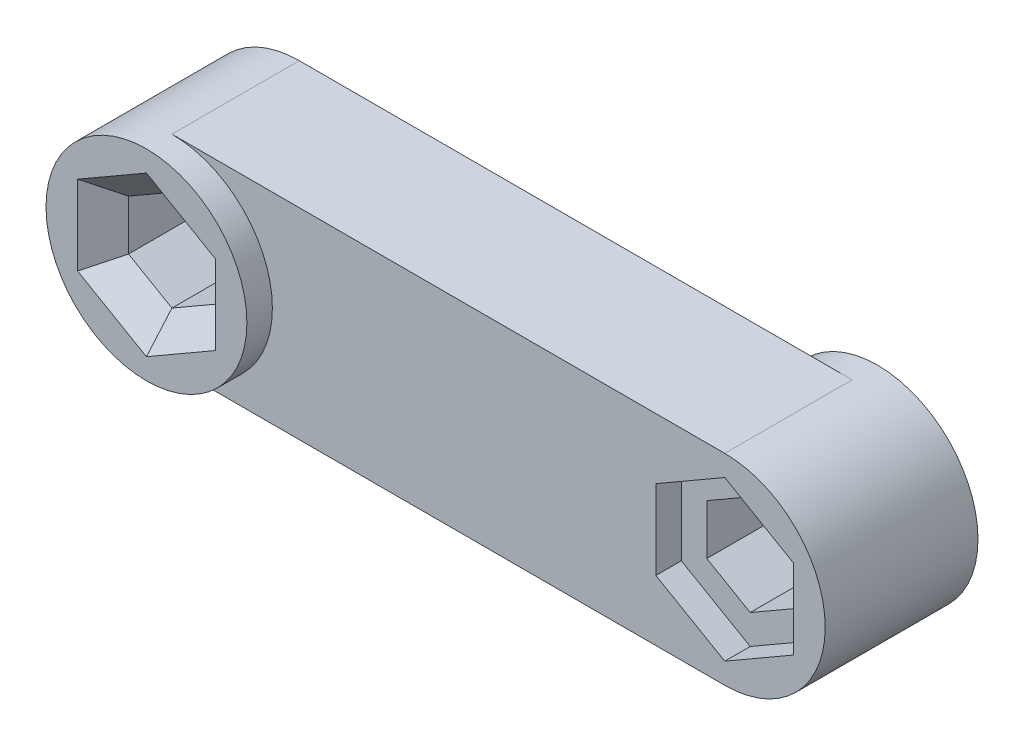
SolidWorks part; units mm, degrees
ref_plane "Plan de face" through (0, 0, 0) normal (1, 0, 0) x (0, 1, 0)
ref_plane "Plan de dessus" through (0, 0, 0) normal (0, 0, 1) x (0, 1, 0)
ref_plane "Plan de droite" through (0, 0, 0) normal (0, 1, 0) x (-1, 0, 0)
sketch "Esquisse1" plane through (0, 0, 0) normal (0, 0, 1) x (0, 1, 0)
  line L0 (0, -21.71) -> (0, 21.71) construction
  line L1 (-7.89, -21.71) -> (-7.89, 21.71)
  line L2 (7.89, -21.71) -> (7.89, 21.71)
  line L3 (0, 0) -> (50.7117, 0) construction
  line L4 (-1.9688, -18.3) -> (-3.9375, -21.71)
  line L5 (-3.9375, -21.71) -> (-1.9688, -25.12)
  line L6 (-1.9688, -25.12) -> (1.9688, -25.12)
  line L7 (1.9688, -25.12) -> (3.9375, -21.71)
  line L8 (3.9375, -21.71) -> (1.9688, -18.3)
  line L9 (1.9688, -18.3) -> (-1.9688, -18.3)
  line L10 (1.9688, 18.3) -> (-1.9688, 18.3)
  line L11 (3.9375, 21.71) -> (1.9688, 18.3)
  line L12 (1.9688, 25.12) -> (3.9375, 21.71)
  line L13 (-1.9688, 25.12) -> (1.9688, 25.12)
  line L14 (-3.9375, 21.71) -> (-1.9688, 25.12)
  line L15 (-1.9688, 18.3) -> (-3.9375, 21.71)
  arc A0 (-7.89, -21.71) -> (7.89, -21.71) centre (0, -21.71) ccw
  arc A1 (7.89, 21.71) -> (-7.89, 21.71) centre (0, 21.71) ccw
  circle A2 centre (0, -21.71) radius 3.41 construction
  circle A3 centre (0, 21.71) radius 3.41 construction
  point P2 (0, 0)
  dimension "D1" = 43.42
  dimension "D2" = 15.78
  dimension "D3" = 6.82
extrude "Boss.-Extru.1" add sketch "Esquisse1" along normal blind 10
sketch "Esquisse3" plane through (0, 0, 0) normal (0, 0, -1) x (1, 0, 0)
  circle A0 centre (21.71, 0) radius 7.89
  line M1 (18.3, -1.9688) -> (18.3, 1.9688)
  line M2 (18.3, 1.9688) -> (21.71, 3.9375)
  line M3 (21.71, 3.9375) -> (25.12, 1.9688)
  line M4 (25.12, 1.9688) -> (25.12, -1.9688)
  line M5 (25.12, -1.9688) -> (21.71, -3.9375)
  line M6 (21.71, -3.9375) -> (18.3, -1.9688)
  arc M7 (21.71, -7.89) -> (21.71, 7.89) centre (21.71, 0) ccw
extrude "Boss.-Extru.3" add sketch "Esquisse3" along normal blind 2 contours A0 M7 M6 M1 M2 M3 M4 M5 region at (27.1313, 5.4213, 0)
sketch "Esquisse4" plane through (0, 0, 10) normal (0, 0, 1) x (1, 0, 0)
  circle A0 centre (-21.71, 0) radius 7.89
  arc A1 (-21.71, 7.89) -> (-21.71, -7.89) centre (-21.71, 0) ccw construction
  arc M4 (-21.71, 7.89) -> (-21.71, -7.89) centre (-21.71, 0) ccw
  line M12 (-25.12, 1.9688) -> (-21.71, 3.9375)
  line M13 (-21.71, 3.9375) -> (-18.3, 1.9688)
  line M14 (-18.3, 1.9688) -> (-18.3, -1.9688)
  line M15 (-18.3, -1.9688) -> (-21.71, -3.9375)
  line M16 (-21.71, -3.9375) -> (-25.12, -1.9688)
  line M17 (-25.12, -1.9688) -> (-25.12, 1.9688)
extrude "Boss.-Extru.4" add sketch "Esquisse4" along normal blind 2 contours A0 M4 M17 M12 M13 M14 M15 M16 region at (-16.2887, -5.4213, 10)
sketch "Esquisse5" plane through (0, 0, 0) normal (0, 0, -1) x (1, 0, 0)
  line L27 (-16.3, -3.1235) -> (-16.3, 3.1235)
  line L28 (-21.71, -6.2469) -> (-16.3, -3.1235)
  line L29 (-27.12, -3.1235) -> (-21.71, -6.2469)
  line L30 (-27.12, 3.1235) -> (-27.12, -3.1235)
  line L31 (-21.71, 6.2469) -> (-27.12, 3.1235)
  line L32 (-16.3, 3.1235) -> (-21.71, 6.2469)
  line L33 (-16.3, -3.1235) -> (-16.3, 3.1235)
  line L34 (-21.71, -6.2469) -> (-16.3, -3.1235)
  line L35 (-27.12, -3.1235) -> (-21.71, -6.2469)
  line L36 (-27.12, 3.1235) -> (-27.12, -3.1235)
  line L37 (-21.71, 6.2469) -> (-27.12, 3.1235)
  line L38 (-16.3, 3.1235) -> (-21.71, 6.2469)
  dimension "D1" = 2
extrude "Enlèv. mat.-Extru.2" cut sketch "Esquisse5" against normal blind 2
sketch "Esquisse6" plane through (0, 0, 10) normal (0, 0, 1) x (1, 0, 0)
  line L27 (27.12, -3.1235) -> (27.12, 3.1235)
  line L28 (21.71, -6.2469) -> (27.12, -3.1235)
  line L29 (16.3, -3.1235) -> (21.71, -6.2469)
  line L30 (16.3, 3.1235) -> (16.3, -3.1235)
  line L31 (21.71, 6.2469) -> (16.3, 3.1235)
  line L32 (27.12, 3.1235) -> (21.71, 6.2469)
  line L33 (27.12, -3.1235) -> (27.12, 3.1235)
  line L34 (21.71, -6.2469) -> (27.12, -3.1235)
  line L35 (16.3, -3.1235) -> (21.71, -6.2469)
  line L36 (16.3, 3.1235) -> (16.3, -3.1235)
  line L37 (21.71, 6.2469) -> (16.3, 3.1235)
  line L38 (27.12, 3.1235) -> (21.71, 6.2469)
  dimension "D1" = 2
extrude "Enlèv. mat.-Extru.3" cut sketch "Esquisse6" against normal blind 2
chamfer "Chanfrein1" distance 2 angle 45 12 edges at (23.415, 2.9531, -2) (25.12, 0, -2) (23.415, -2.9531, -2) (20.005, -2.9531, -2) (18.3, 0, -2) (20.005, 2.9531, -2) (-23.415, -2.9531, 12) (-20.005, -2.9531, 12) (-18.3, 0, 12) (-20.005, 2.9531, 12) (-23.415, 2.9531, 12) (-25.12, 0, 12)
